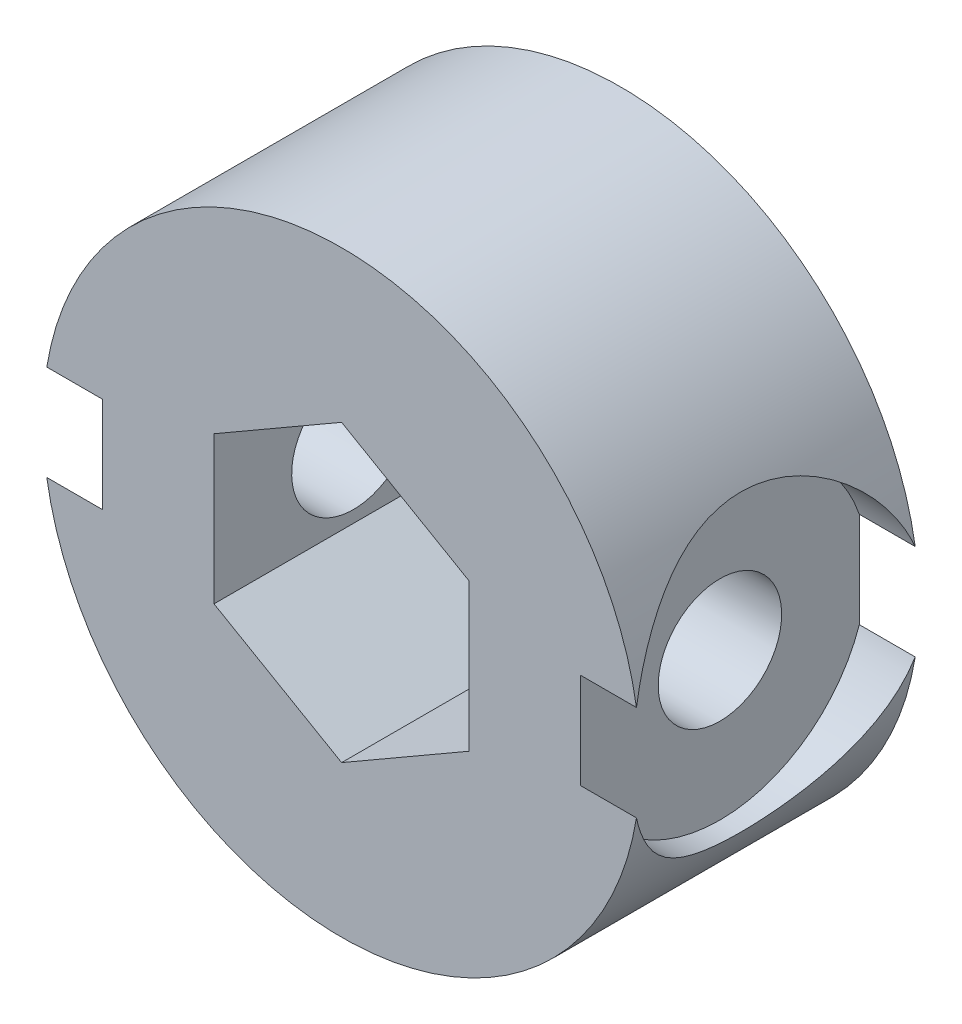
SolidWorks part; units mm, degrees
ref_plane "Front Plane" through (0, 0, 0) normal (0, 0, 1) x (1, 0, 0)
ref_plane "Top Plane" through (0, 0, 0) normal (0, 1, 0) x (1, 0, 0)
ref_plane "Right Plane" through (0, 0, 0) normal (1, 0, 0) x (0, 0, -1)
sketch "Sketch1" plane through (0, 0, 0) normal (0, 0, 1) x (1, 0, 0)
  line L0 (0, -3.7) -> (0, 3.7) construction
  line L1 (-3.2043, -1.85) -> (3.2043, 1.85) construction
  line L8 (3.2043, -1.85) -> (-3.2043, 1.85) construction
  line L9 (0, 3.7) -> (3.2043, 1.85)
  line L10 (3.2043, 1.85) -> (3.2043, -1.85)
  line L11 (3.2043, -1.85) -> (0, -3.7)
  line L12 (0, -3.7) -> (-3.2043, -1.85)
  line L13 (-3.2043, -1.85) -> (-3.2043, 1.85)
  line L14 (-3.2043, 1.85) -> (0, 3.7)
  circle A0 centre (0, 0) radius 7.5
  circle A1 centre (0, 0) radius 3.7 construction
  point P6 (0, 0)
  point P10 (0, 0)
  point P13 (0, 0)
extrude "Boss-Extrude2" add sketch "Sketch1" along normal blind 7
ref_plane "Plane1" through (0, 0, 0) normal (-1, 0, 0) x (0, 0, 1)
sketch "Sketch2" plane through (0, 0, 0) normal (-1, 0, 0) x (0, 0, 1)
  line L0 (0, 0) -> (7, 0) construction
  line L1 (7, -7.5) -> (7, 7.5) construction
  circle A0 centre (3.5, 0) radius 1.55
extrude "Cut-Extrude1" cut sketch "Sketch2" against normal blind 7.5 and the other way blind 7.5
ref_plane "Plane2" through (-6, 0, 0) normal (-1, 0, 0) x (0, 0, 1)
ref_plane "Plane3" through (6, 0, 0) normal (-1, 0, 0) x (0, 0, 1)
sketch "Sketch4" plane through (-6, 0, 0) normal (-1, 0, 0) x (0, 0, 1)
  circle A0 centre (3.5, 0) radius 3.7
extrude "Cut-Extrude2" cut sketch "Sketch4" along normal blind 4
sketch "Sketch5" plane through (6, 0, 0) normal (-1, 0, 0) x (0, 0, 1)
  circle A0 centre (3.5, 0) radius 3.7
extrude "Cut-Extrude3" cut sketch "Sketch5" against normal blind 4
